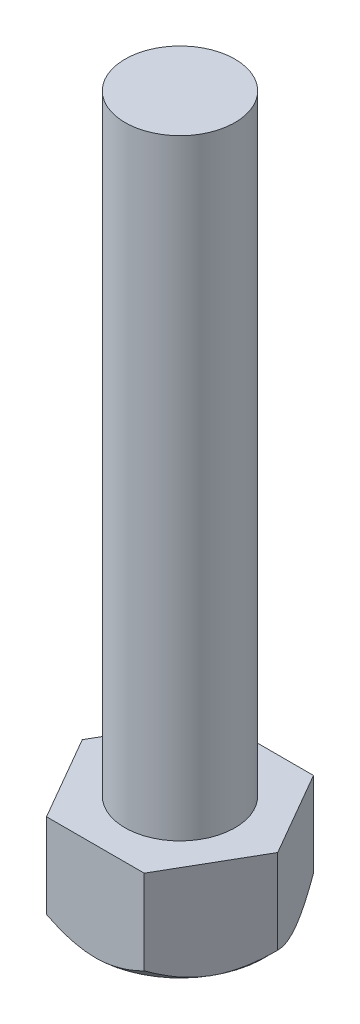
SolidWorks part; units mm, degrees
ref_plane "Front Plane" through (0, 0, 0) normal (0, 0, 1) x (1, 0, 0)
ref_plane "Top Plane" through (0, 0, 0) normal (0, 1, 0) x (1, 0, 0)
ref_plane "Right Plane" through (0, 0, 0) normal (1, 0, 0) x (0, 0, -1)
sketch "Sketch1" plane through (0, 0, 0) normal (0, 1, 0) x (1, 0, 0)
  line L1 (-2, -3.4641) -> (2, -3.4641)
  line L2 (2, -3.4641) -> (4, 0)
  line L3 (4, 0) -> (2, 3.4641)
  line L4 (2, 3.4641) -> (-2, 3.4641)
  line L5 (-2, 3.4641) -> (-4, 0)
  line L6 (-4, 0) -> (-2, -3.4641)
  circle A0 centre (0, 0) radius 3.4641 construction
  circle A1 centre (0, 0) radius 2.25
  dimension "D2" = 4.5
  dimension "D1" = 8
extrude "Boss-Extrude1" add sketch "Sketch1" along normal blind 4 contours L1 L2 L3 L4 L5 L6
extrude "Boss-Extrude2" add sketch "Sketch1<3>" along normal blind 29 contours A1
sketch "Sketch1<3>" plane through (0, 0, 0) normal (0, 1, 0) x (1, 0, 0) same geometry as "Sketch1"
sketch "Sketch3" plane through (0, 0, 0) normal (0, -1, 0) x (1, 0, 0)
  circle A0 centre (0, 0) radius 3.4641
extrude "Cut-Extrude6" cut sketch "Sketch3" against normal blind 1 draft 45 flip side to cut
